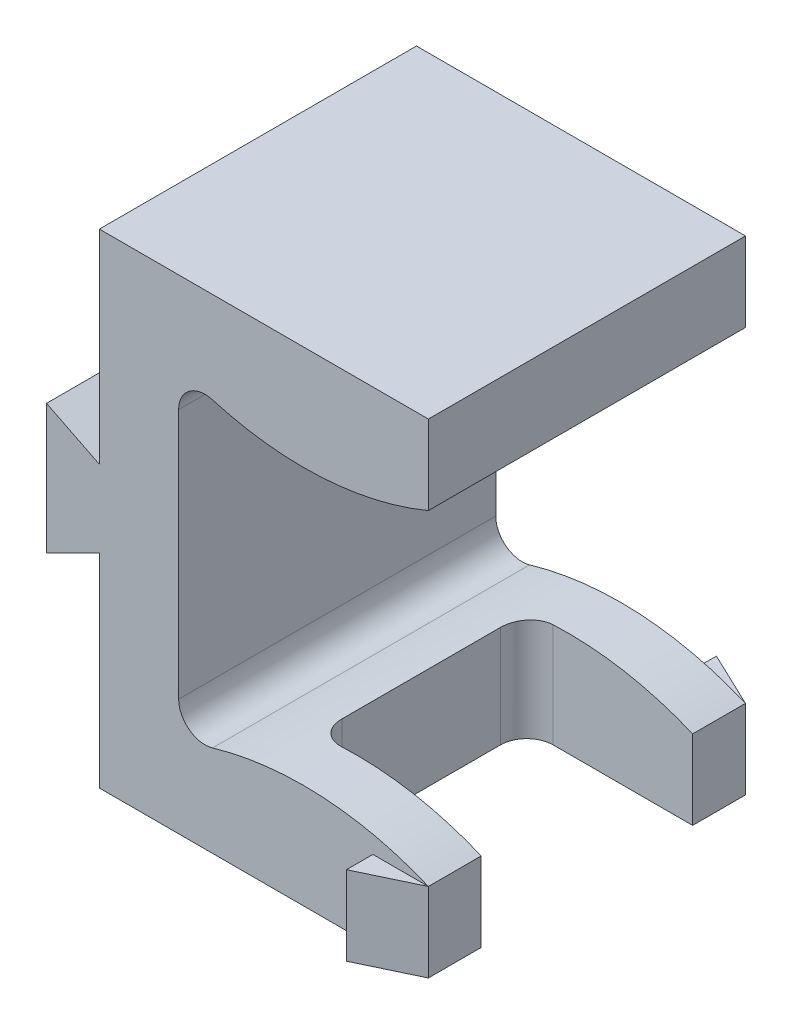
SolidWorks part; units mm, degrees
ref_plane "Front Plane" through (0, 0, 0) normal (0, 0, 1) x (1, 0, 0)
ref_plane "Top Plane" through (0, 0, 0) normal (0, 1, 0) x (1, 0, 0)
ref_plane "Right Plane" through (0, 0, 0) normal (1, 0, 0) x (0, 0, -1)
sketch "Sketch1" plane through (0, 0, 0) normal (0, 0, 1) x (1, 0, 0)
  line L2 (-159.7982, 9.1594) -> (-172.2482, 9.1594)
  line L3 (-172.2482, 9.1594) -> (-172.2482, -9.1594)
  line L7 (-169.2482, -22.8519) -> (-169.2482, 6.1594) construction
  line L12 (-169.2482, 5.1594) -> (-169.2482, 1.9844) construction
  line L13 (-142.8048, 5.1594) -> (-142.8048, -5.1594) construction
  line L15 (-156.5482, 5.1594) -> (21.2518, 5.1594) construction
  line L16 (-156.5482, -5.1594) -> (21.2518, -5.1594) construction
  line L23 (-159.7982, 6.1594) -> (-159.7982, 9.1594)
  line L28 (-164.5232, 5.2094) -> (-144.5007, 5.2094) construction
  line L29 (-156.5482, 5.1594) -> (-169.2482, 5.1594) construction
  line L30 (-169.2482, 6.1594) -> (-169.2482, 5.1594)
  line L34 (-169.2482, 5.1594) -> (-169.2482, -5.1594)
  line L35 (-172.2482, 0) -> (-169.2482, 0) construction
  line L36 (-169.2482, -6.1594) -> (-169.2482, -5.1594)
  line L37 (-159.7982, -6.1594) -> (-159.7982, -9.1594)
  line L38 (-159.7982, -9.1594) -> (-172.2482, -9.1594)
  line L39 (-159.7982, 5.1594) -> (-159.7982, 1.9844) construction
  arc A5 (-169.2482, 6.1594) -> (-159.7982, 6.1594) centre (-164.5232, 17.4347) ccw
  arc A6 (-169.2482, -6.1594) -> (-159.7982, -6.1594) centre (-164.5232, -17.4347) cw
  point P30 (-142.8048, 0)
  dimension "D4" = 3
  dimension "D3" = 3
  dimension "D1" = 0.05
  dimension "D2" = 1
extrude "MainBody" add sketch "Sketch1" along normal mid plane 12
sketch "Sketch3" plane through (0, -9.1594, 0) normal (0, -1, 0) x (1, 0, 0)
  line L0 (-159.7982, -6) -> (-161.8982, -7)
  line L1 (-161.8982, -7) -> (-161.8982, -6)
  line L2 (-172.2482, -6) -> (-159.7982, -6) construction
  line L3 (-161.8982, -6) -> (-159.7982, -6)
  line L4 (-162.8982, -12.7) -> (-162.8982, -6.35) construction
  line L5 (10.0753, 0) -> (-10.0753, 0) construction
  line L6 (-161.8982, 6) -> (-159.7982, 6)
  line L7 (-161.8982, 7) -> (-161.8982, 6)
  line L8 (-159.7982, 6) -> (-161.8982, 7)
  dimension "D1" = 1
  dimension "D2" = 1
extrude "Hook" add sketch "Sketch3" against normal up to vertex (3 mm away) up to point (-159.7982, -6.1594, -6)
sketch "Sketch4" plane through (0, -9.1594, 0) normal (0, -1, 0) x (1, 0, 0)
  line L0 (-159.7982, 6) -> (-159.7982, -6) construction
  line L1 (-159.7982, 4) -> (-166.0732, 4)
  line L2 (-159.7982, 4) -> (-159.7982, -4)
  line L3 (-159.7982, -4) -> (-166.0732, -4)
  line L4 (-166.0732, 4) -> (-166.0732, -4)
  line L5 (-172.2482, 6) -> (-172.2482, -6) construction
  line L6 (-172.2482, -6) -> (-161.8982, -6) construction
  line L7 (-162.8982, -6.35) -> (-169.2482, -6.35) construction
  point P6 (-166.0732, 0)
  point P9 (-172.2482, 0)
  point P14 (-166.0732, -6.35)
  dimension "D1" = 2
extrude "Flex" cut sketch "Sketch4" against normal up to next
fillet "Fillet1" radius 1 2 edges at (-166.0732, -7.2337, -4) (-166.0732, -7.2337, 4)
fillet "Fillet2" radius 1 2 edges at (-169.2482, 6.1594, 0) (-169.2482, -6.1594, 0)
sketch "Sketch5" [suppressed] plane through (-172.2482, 0, 0) normal (-1, 0, 0) x (0, 0, 1)
  line L1 (-6, 9.1594) -> (6, 9.1594)
  line L2 (-6, 9.1594) -> (-6, -9.1594)
  line L3 (-6, -9.1594) -> (6, -9.1594)
  line L4 (6, 9.1594) -> (6, -9.1594)
extrude "Boss-Extrude1" [suppressed] add sketch "Sketch5" along normal blind 15
sketch "Sketch6" [suppressed] plane through (0, 9.1594, 0) normal (0, 1, 0) x (1, 0, 0)
  line L0 (-187.2482, -6) -> (-187.2482, 6) construction
  circle A0 centre (-182.2482, 0) radius 3.302
  dimension "D1" = 6.604
  dimension "D2" = 5
extrude "Cut-Extrude2" [suppressed] cut sketch "Sketch6" against normal through all
sketch "Sketch7" plane through (-172.2482, 0, 0) normal (-1, 0, 0) x (0, 0, 1)
  circle A0 centre (0, 0) radius 1.5
  dimension "D1" = 3
extrude "Boss-Extrude2" [suppressed] add sketch "Sketch7" along normal blind 5
fillet "Fillet3" [suppressed] radius 1
sketch "Sketch8" plane through (0, 0, 6) normal (0, 0, 1) x (1, 0, 0)
  line L0 (-172.2482, -1.45) -> (-172.2482, 1.45)
  line L1 (-172.2482, 9.1594) -> (-172.2482, -9.1594) construction
  line L2 (-172.2482, 1.45) -> (-174.2482, 2.45)
  line L3 (-174.2482, 2.45) -> (-174.2482, -2.45)
  line L4 (-174.2482, -2.45) -> (-172.2482, -1.45)
  point P6 (-174.2482, 0)
  point P7 (-172.2482, 0)
  point P8 (-172.2482, 0)
  dimension "D1" = 4.9
  dimension "D2" = 2.9
  dimension "D3" = 2
extrude "Slot" add sketch "Sketch8" against normal up to surface (12 mm away) up to face at (-165.6835, -0.5599, -6)
equation "\"HookThickness\"= 3mm"
equation "\"D3@Sketch1\"=\"HookThickness\""
equation "\"D4@Sketch1\"=\"HookThickness\""
equation "\"CylinderDiameter\"=3"
equation "\"D1@Sketch7\"=\"CylinderDiameter\""
